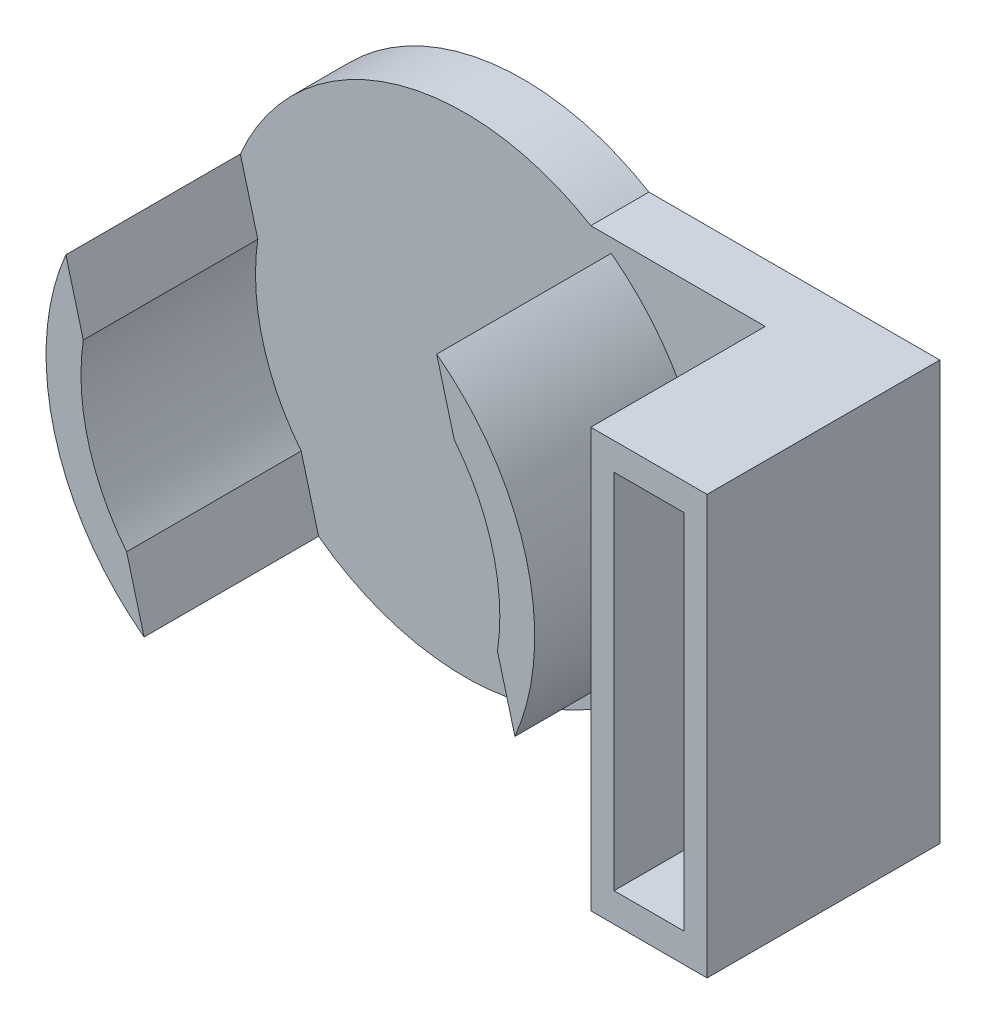
SolidWorks part; units mm, degrees
ref_plane "Piano frontale" through (0, 0, 0) normal (0, 0, 1) x (1, 0, 0)
ref_plane "Piano superiore" through (0, 0, 0) normal (0, 1, 0) x (1, 0, 0)
ref_plane "Piano destro" through (0, 0, 0) normal (1, 0, 0) x (0, 0, -1)
sketch "Schizzo1" plane through (0, 0, 0) normal (0, 0, 1) x (1, 0, 0)
  line L0 (22.3655, 11.6094) -> (47.3655, 11.6094) construction
  line L1 (22.3655, -24.3906) -> (47.3655, -24.3906)
  line L2 (47.3655, -24.3906) -> (47.3655, 11.6094)
  line L3 (47.3655, 11.6094) -> (22.3655, 11.6094)
  arc A2 (22.3655, 11.6094) -> (22.3655, -24.3906) centre (11.5488, -6.3906) ccw
  dimension "D1" = 25
  dimension "D3" = 42
  dimension "D2" = 36
extrude "Estrusione-Estrusione1" add sketch "Schizzo1" along normal mid plane 5
sketch "Schizzo2" plane through (0, 0, 2.5) normal (0, 0, 1) x (1, 0, 0)
  line L1 (37.3655, 11.6094) -> (47.3655, 11.6094)
  line L2 (37.3655, 11.6094) -> (37.3655, -24.3906)
  line L3 (37.3655, -24.3906) -> (47.3655, -24.3906)
  line L4 (47.3655, 11.6094) -> (47.3655, -24.3906)
  line L5 (37.3655, 11.6094) -> (47.3655, -24.3906) construction
  line L6 (37.3655, -24.3906) -> (47.3655, 11.6094) construction
  point P0 (42.3655, -6.3906)
  point P6 (22.3655, 11.6094)
  point P8 (0, 0)
  dimension "D1" = 10
extrude "Estrusione-Estrusione2" add sketch "Schizzo2" along normal blind 15
sketch "Schizzo3" plane through (0, 0, 17.5) normal (0, 0, 1) x (1, 0, 0)
  line L1 (39.3655, 9.2594) -> (45.3655, 9.2594)
  line L2 (39.3655, 9.2594) -> (39.3655, -21.8906)
  line L3 (39.3655, -21.8906) -> (45.3655, -21.8906)
  line L4 (45.3655, 9.2594) -> (45.3655, -21.8906)
  line L5 (39.3655, 9.2594) -> (45.3655, -21.8906) construction
  line L6 (39.3655, -21.8906) -> (45.3655, 9.2594) construction
  line L7 (47.3655, -24.3906) -> (47.3655, 11.6094) construction
  line L8 (37.3655, -24.3906) -> (47.3655, -24.3906) construction
  point P0 (42.3655, -6.3156)
  dimension "D1" = 6
  dimension "D2" = 2
  dimension "D3" = 31.15
  dimension "D4" = 2.5
extrude "Taglio-Estrusione1" cut sketch "Schizzo3" against normal blind 13
sketch "Schizzo5" plane through (0, 0, 2.5) normal (0, 0, 1) x (1, 0, 0)
  line L0 (37.3655, -6.3906) -> (-9.4512, -6.3906) construction
  line L1 (37.3655, 11.6094) -> (37.3655, -24.3906) construction
  line L3 (11.5488, -27.3906) -> (11.5488, 14.6094) construction
  arc A0 (22.3655, 11.6094) -> (22.3655, -24.3906) centre (11.5488, -6.3906) ccw construction
  circle A1 centre (11.5488, -6.3906) radius 21
extrude "Estrusione-Sottile1" add sketch "Schizzo5" along normal blind 15 thin thin type one direction reverse wall 3
sketch "Schizzo7" plane through (0, 0, 4.5) normal (0, 0, 1) x (1, 0, 0)
  line L0 (39.3655, -21.8906) -> (45.3655, -20.283) construction
  line L1 (45.3655, -21.8906) -> (45.3655, 9.2594) construction
  line L2 (39.3655, -21.8906) -> (38.3708, -18.1785) construction
  line L3 (39.3655, -21.8906) -> (45.3655, -21.8906) construction
  line L4 (45.3655, -21.8906) -> (39.3655, -21.8906) construction
  dimension "D1" = 15
ref_plane "Piano1" through (-3.0639, 11.4347, 0) normal (-0.2588, 0.9659, 0) x (0.9659, 0.2588, 0)
sketch "Schizzo8" plane through (-3.0639, 11.4347, 0) normal (-0.2588, 0.9659, 0) x (0.9659, 0.2588, 0)
  line L6 (9.5013, -17.5) -> (9.5013, 2.5) construction
  line L7 (-11.4987, -17.5) -> (30.5013, -17.5) construction
  line L8 (24.6081, 2.5) -> (-11.4987, 2.5) construction
  line L9 (-6.9987, -17.5) -> (26.0013, -17.5)
  line L10 (26.0013, -17.5) -> (26.0013, -2.5)
  line L11 (15.2906, -2.5) -> (30.5013, -2.5) construction
  line L12 (26.0013, -2.5) -> (-6.9987, -2.5)
  line L13 (-6.9987, -2.5) -> (-6.9987, -17.5)
  dimension "D1" = 16.5
  dimension "D2" = 33
extrude "Taglio-Estrusione2" cut sketch "Schizzo8" against normal through all
